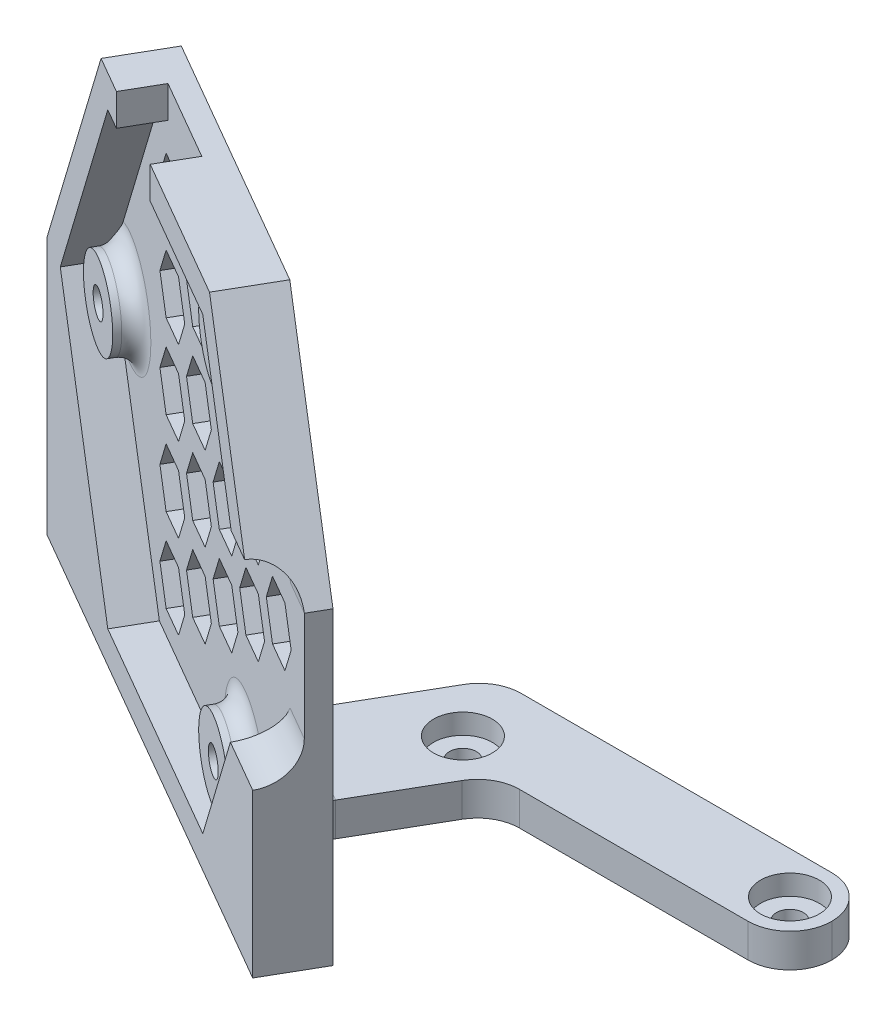
SolidWorks part; units mm, degrees
ref_plane "Plan de face" through (0, 0, 0) normal (0, 0, 1) x (1, 0, 0)
ref_plane "Plan de dessus" through (0, 0, 0) normal (0, 1, 0) x (1, 0, 0)
ref_plane "Plan de droite" through (0, 0, 0) normal (1, 0, 0) x (0, 0, -1)
sketch "Esquisse1" plane through (0, 0, 0) normal (0, -1, 0) x (1, 0, 0)
  line L0 (-1.5106, -613.3585) -> (-0.6906, -614.7787) construction
  line L1 (-0.6906, -614.7787) -> (25.2902, -599.7787) construction
  line L2 (25.2902, -599.7787) -> (24.4702, -598.3585) construction
  line L3 (24.4702, -598.3585) -> (-1.5106, -613.3585) construction
  circle A0 centre (30.4658, -623.4307) radius 1.7
  circle A1 centre (66.5558, -626.3007) radius 1.7
  circle A3 centre (5.084, -609.1007) radius 5 construction
  dimension "D1" = 30
  dimension "D2" = 30
  dimension "D3" = 7.84
  dimension "D4" = 1.64
  dimension "D5" = 0.39
ref_plane "Plan1" through (266.0344, 0, -460.785) normal (-0.5, 0, 0.866) x (0.866, 0, 0.5)
ref_plane "Plan2" through (267.4294, 0, -463.2012) normal (-0.5, 0, 0.866) x (0.866, 0, 0.5)
sketch "Esquisse2" plane through (684.9869, 0, -222.1243) normal (0.5, 0, -0.866) x (-0.866, 0, -0.5)
  line L19 (775.1414, 56.5615) -> (775.1414, 4.6) construction
  line L20 (776.8014, 58.1615) -> (776.8014, 56.5615) construction
  line L21 (787.8014, 56.5615) -> (776.8014, 56.5615) construction
  line L22 (787.8014, 58.1615) -> (787.8014, 56.5615) construction
  line L23 (787.8014, 58.1615) -> (776.8014, 58.1615) construction
  line L24 (748.0281, 35.5808) -> (760.1414, 56.5615) construction
  line L25 (760.1414, 4.6) -> (748.0281, 25.5808) construction
  line L26 (790.1414, 4.6) -> (760.1414, 4.6) construction
  line L27 (805.1414, 30.5808) -> (790.1414, 4.6) construction
  line L28 (790.1414, 56.5615) -> (805.1414, 30.5808) construction
  line L29 (760.1414, 56.5615) -> (790.1414, 56.5615) construction
  line L30 (748.0281, 35.5808) -> (748.0281, 25.5808) construction
  line L31 (790.1414, 0) -> (760.1414, 0) construction
  point P1 (787.8014, 57.3615)
  dimension "D1" = 30
  dimension "D2" = 20.9808
  dimension "D3" = 10
  dimension "D4" = 20.9808
  dimension "D5" = 30
  dimension "D6" = 30
  dimension "D7" = 30
  dimension "D8" = 51.9615
  dimension "D9" = 120
  dimension "D10" = 120
  dimension "D11" = 120
  dimension "D12" = 120
  dimension "D13" = 120
  dimension "D14" = 150
  dimension "D15" = 150
  dimension "D16" = 15
  dimension "D17" = 2.34
  dimension "D18" = 11
  dimension "D19" = 1.6
  dimension "D20" = 11
  dimension "D21" = 1.6
  dimension "D22" = 90
  dimension "D23" = 90
  dimension "D24" = 0
  dimension "D25" = 4.6
  dimension "D26" = 0
  dimension "D27" = 0
sketch "Esquisse3" plane through (267.4294, 0, -463.2012) normal (-0.5, 0, 0.866) x (0.866, 0, 0.5)
  line L7 (-275.3316, 61.1615) -> (-310.6433, 61.1615)
  line L8 (-310.6433, 61.1615) -> (-328.2991, 30.5808)
  line L9 (-328.2991, 30.5808) -> (-310.6433, 0)
  line L10 (-310.6433, 0) -> (-275.3316, 0)
  line L11 (-275.3316, 0) -> (-261.2742, 24.3482)
  line L12 (-261.2742, 24.3482) -> (-261.2742, 36.8133)
  line L13 (-261.2742, 36.8133) -> (-275.3316, 61.1615)
  line L14 (-277.5256, 57.3615) -> (-308.4493, 57.3615)
  line L15 (-265.0742, 35.7951) -> (-277.5256, 57.3615)
  line L16 (-265.0742, 25.3664) -> (-265.0742, 35.7951)
  line L17 (-277.5256, 3.8) -> (-265.0742, 25.3664)
  line L18 (-308.4493, 3.8) -> (-277.5256, 3.8)
  line L19 (-323.9112, 30.5808) -> (-308.4493, 3.8)
  line L20 (-308.4493, 57.3615) -> (-323.9112, 30.5808)
  line L21 (-277.5256, 57.3615) -> (-308.4493, 57.3615)
  line L22 (-265.0742, 35.7951) -> (-277.5256, 57.3615)
  line L23 (-265.0742, 25.3664) -> (-265.0742, 35.7951)
  line L24 (-277.5256, 3.8) -> (-265.0742, 25.3664)
  line L25 (-308.4493, 3.8) -> (-277.5256, 3.8)
  line L26 (-323.9112, 30.5808) -> (-308.4493, 3.8)
  line L27 (-308.4493, 57.3615) -> (-323.9112, 30.5808)
  line L28 (28.092, 0) -> (-28.092, 0) construction
  dimension "D2" = 0
  dimension "D1" = 0.8
extrude "Boss.-Extru.1" add sketch "Esquisse3" along normal blind 4.5
sketch "Esquisse4" plane through (267.4294, 0, -463.2012) normal (-0.5, 0, 0.866) x (0.866, 0, 0.5)
  line L0 (-310.6433, 61.1615) -> (-275.3316, 61.1615)
  line L1 (-275.3316, 61.1615) -> (-261.2742, 36.8133)
  line L2 (-261.2742, 36.8133) -> (-261.2742, 24.3482)
  line L3 (-261.2742, 24.3482) -> (-275.3316, 0)
  line L4 (-275.3316, 0) -> (-310.6433, 0)
  line L5 (-310.6433, 0) -> (-328.2991, 30.5808)
  line L6 (-328.2991, 30.5808) -> (-310.6433, 61.1615)
extrude "Boss.-Extru.2" add sketch "Esquisse4" against normal blind 2.5
sketch "Esquisse5" plane through (267.4294, 0, -463.2012) normal (-0.5, 0, 0.866) x (0.866, 0, 0.5)
  line L0 (-305.6475, 57.3615) -> (-305.6475, 61.1615)
  line L1 (-305.6475, 58.1615) -> (-305.6475, 56.5615) construction
  line L2 (-275.3316, 61.1615) -> (-310.6433, 61.1615) construction
  line L3 (-305.6475, 61.1615) -> (-294.6475, 61.1615)
  line L4 (-294.6475, 61.1615) -> (-294.6475, 57.3615)
  line L5 (-294.6475, 58.1615) -> (-294.6475, 56.5615) construction
  line L6 (-294.6475, 57.3615) -> (-305.6475, 57.3615)
extrude "Enlèv. mat.-Extru.1" cut sketch "Esquisse5" along normal up to next
sketch "Esquisse6" plane through (267.4294, 0, -463.2012) normal (-0.5, 0, 0.866) x (0.866, 0, 0.5)
  line L0 (-292.9875, 30.5808) -> (-280.4875, 52.2314) construction
  line L1 (-292.9875, 56.5615) -> (-292.9875, 4.6) construction
  line L2 (-292.9875, 30.5808) -> (-280.4875, 8.9301) construction
  line L3 (-292.9875, 30.5808) -> (-317.9875, 30.5808) construction
  circle A0 centre (-280.4875, 52.2314) radius 4.75
  circle A1 centre (-280.4875, 8.9301) radius 4.75
  circle A2 centre (-317.9875, 30.5808) radius 4.75
  dimension "D6" = 9.5
  dimension "D7" = 9.5
  dimension "D8" = 9.5
  dimension "D1" = 25
  dimension "D2" = 25
  dimension "D3" = 25
  dimension "D4" = 120
  dimension "D5" = 120
extrude "Boss.-Extru.3" add sketch "Esquisse6" along normal up to surface (2.79 mm away) up to plane "Plan1"
sketch "Esquisse7" plane through (267.4294, 0, -463.2012) normal (-0.5, 0, 0.866) x (0.866, 0, 0.5)
  line L0 (-328.2991, 30.5808) -> (-328.2991, 0)
  line L1 (-328.2991, 0) -> (-310.6433, 0)
  line L2 (-310.6433, 0) -> (-328.2991, 30.5808)
  line L3 (-275.3316, 0) -> (-261.2742, 24.3482)
  line L4 (-261.2742, 24.3482) -> (-261.2742, 0)
  line L5 (-261.2742, 0) -> (-275.3316, 0)
  dimension "D2" = 14.0574
extrude "Boss.-Extru.4" add sketch "Esquisse7" along normal up to surface (4.5 mm away) and the other way up to surface (2.5 mm away) up to face at (12.6176, 36.9543, -605.1207) other way up to face at (18.4231, 30.5808, -609.8518)
hole_wizard "Dégagement M31" positions "Esquisse9" profile "Esquisse10" hole size "M3" standard "Ansi Metric"
sketch "Esquisse9" plane through (266.0344, 0, -460.785) normal (-0.5, 0, 0.866) x (0.866, 0, 0.5)
  point P0 (-317.9875, 30.5808)
  point P3 (-280.4875, 52.2314)
  point P6 (-280.4875, 8.9301)
sketch "Esquisse10" plane through (-9.3509, 30.5808, -619.7787) normal (0, 1, 0) x (0.866, 0, 0.5)
  line L0 (0, 0) -> (0, 3.9614)
  line L1 (0, 3.9614) -> (1.6, 3)
  line L2 (1.6, 3) -> (1.6, 0)
  line L5 (1.6, 0) -> (0, 0)
  line L10 (0, 3.9614) -> (-1.6, 3) construction
  line L11 (0, -6.35) -> (0, 107.95) construction
  dimension "Diamètre du perçage" = 3.2
  dimension "Profondeur du perçage" = 3
  dimension "Angle de pointe" = 118
sketch "Esquisse11" plane through (143.5957, 0, -534.6966) normal (-0.5, 0, 0.866) x (0.866, 0, 0.5)
  line L0 (-162.6567, 56.5615) -> (-151.6567, 56.5615) construction
  line L1 (-159.2247, 53.5615) -> (-163.2647, 53.5615)
  line L2 (-163.2647, 53.5615) -> (-165.2847, 50.0628)
  line L3 (-165.2847, 50.0628) -> (-163.2647, 46.564)
  line L4 (-163.2647, 46.564) -> (-159.2247, 46.564)
  line L5 (-159.2247, 46.564) -> (-157.2047, 50.0628)
  line L6 (-157.2047, 50.0628) -> (-159.2247, 53.5615)
  line L7 (-164.9967, 56.5615) -> (-179.9967, 30.5808) construction
  line L8 (-150.5666, 41.5653) -> (-148.5466, 45.064)
  line L9 (-148.5466, 45.064) -> (-150.5666, 48.5628)
  line L10 (-150.5666, 48.5628) -> (-154.6066, 48.5628)
  line L11 (-154.6066, 48.5628) -> (-156.6266, 45.064)
  line L12 (-156.6266, 45.064) -> (-154.6066, 41.5653)
  line L13 (-154.6066, 41.5653) -> (-150.5666, 41.5653)
  line L14 (-141.9085, 36.5666) -> (-139.8885, 40.0653)
  line L15 (-139.8885, 40.0653) -> (-141.9085, 43.564)
  line L16 (-141.9085, 43.564) -> (-145.9485, 43.564)
  line L17 (-145.9485, 43.564) -> (-147.9685, 40.0653)
  line L18 (-147.9685, 40.0653) -> (-145.9485, 36.5666)
  line L19 (-145.9485, 36.5666) -> (-141.9085, 36.5666)
  line L20 (-133.2504, 31.5678) -> (-131.2304, 35.0666)
  line L21 (-131.2304, 35.0666) -> (-133.2504, 38.5653)
  line L22 (-133.2504, 38.5653) -> (-137.2904, 38.5653)
  line L23 (-137.2904, 38.5653) -> (-139.3104, 35.0666)
  line L24 (-139.3104, 35.0666) -> (-137.2904, 31.5678)
  line L25 (-137.2904, 31.5678) -> (-133.2504, 31.5678)
  line L26 (-124.5924, 26.5691) -> (-122.5724, 30.0678)
  line L27 (-122.5724, 30.0678) -> (-124.5924, 33.5666)
  line L28 (-124.5924, 33.5666) -> (-128.6324, 33.5666)
  line L29 (-128.6324, 33.5666) -> (-130.6524, 30.0678)
  line L30 (-130.6524, 30.0678) -> (-128.6324, 26.5691)
  line L31 (-128.6324, 26.5691) -> (-124.5924, 26.5691)
  line L32 (-159.2247, 26.5691) -> (-157.2047, 30.0678)
  line L33 (-157.2047, 30.0678) -> (-159.2247, 33.5666)
  line L34 (-159.2247, 33.5666) -> (-163.2647, 33.5666)
  line L35 (-163.2647, 33.5666) -> (-165.2847, 30.0678)
  line L36 (-165.2847, 30.0678) -> (-163.2647, 26.5691)
  line L37 (-163.2647, 26.5691) -> (-159.2247, 26.5691)
  line L38 (-150.5666, 21.5703) -> (-148.5466, 25.0691)
  line L39 (-148.5466, 25.0691) -> (-150.5666, 28.5678)
  line L40 (-150.5666, 28.5678) -> (-154.6066, 28.5678)
  line L41 (-154.6066, 28.5678) -> (-156.6266, 25.0691)
  line L42 (-156.6266, 25.0691) -> (-154.6066, 21.5703)
  line L43 (-154.6066, 21.5703) -> (-150.5666, 21.5703)
  line L44 (-141.9085, 16.5716) -> (-139.8885, 20.0703)
  line L45 (-139.8885, 20.0703) -> (-141.9085, 23.5691)
  line L46 (-141.9085, 23.5691) -> (-145.9485, 23.5691)
  line L47 (-145.9485, 23.5691) -> (-147.9685, 20.0703)
  line L48 (-147.9685, 20.0703) -> (-145.9485, 16.5716)
  line L49 (-145.9485, 16.5716) -> (-141.9085, 16.5716)
  line L50 (-159.2247, 6.5741) -> (-157.2047, 10.0728)
  line L51 (-157.2047, 10.0728) -> (-159.2247, 13.5716)
  line L52 (-159.2247, 13.5716) -> (-163.2647, 13.5716)
  line L53 (-163.2647, 13.5716) -> (-165.2847, 10.0728)
  line L54 (-165.2847, 10.0728) -> (-163.2647, 6.5741)
  line L55 (-163.2647, 6.5741) -> (-159.2247, 6.5741)
  line L56 (-150.5666, 38.5653) -> (-154.6066, 38.5653)
  line L57 (-159.2247, 43.564) -> (-163.2647, 43.564)
  line L58 (-163.2647, 43.564) -> (-165.2847, 40.0653)
  line L59 (-165.2847, 40.0653) -> (-163.2647, 36.5666)
  line L60 (-163.2647, 36.5666) -> (-159.2247, 36.5666)
  line L61 (-159.2247, 36.5666) -> (-157.2047, 40.0653)
  line L62 (-157.2047, 40.0653) -> (-159.2247, 43.564)
  line L63 (-154.6066, 38.5653) -> (-156.6266, 35.0666)
  line L64 (-156.6266, 35.0666) -> (-154.6066, 31.5678)
  line L65 (-154.6066, 31.5678) -> (-150.5666, 31.5678)
  line L66 (-150.5666, 31.5678) -> (-148.5466, 35.0666)
  line L67 (-148.5466, 35.0666) -> (-150.5666, 38.5653)
  line L68 (-141.9085, 33.5666) -> (-145.9485, 33.5666)
  line L69 (-145.9485, 33.5666) -> (-147.9685, 30.0678)
  line L70 (-147.9685, 30.0678) -> (-145.9485, 26.5691)
  line L71 (-145.9485, 26.5691) -> (-141.9085, 26.5691)
  line L72 (-141.9085, 26.5691) -> (-139.8885, 30.0678)
  line L73 (-139.8885, 30.0678) -> (-141.9085, 33.5666)
  line L74 (-133.2504, 28.5678) -> (-137.2904, 28.5678)
  line L75 (-137.2904, 28.5678) -> (-139.3104, 25.0691)
  line L76 (-139.3104, 25.0691) -> (-137.2904, 21.5703)
  line L77 (-137.2904, 21.5703) -> (-133.2504, 21.5703)
  line L78 (-133.2504, 21.5703) -> (-131.2304, 25.0691)
  line L79 (-131.2304, 25.0691) -> (-133.2504, 28.5678)
  line L80 (-159.2247, 23.5691) -> (-163.2647, 23.5691)
  line L81 (-163.2647, 23.5691) -> (-165.2847, 20.0703)
  line L82 (-165.2847, 20.0703) -> (-163.2647, 16.5716)
  line L83 (-163.2647, 16.5716) -> (-159.2247, 16.5716)
  line L84 (-159.2247, 16.5716) -> (-157.2047, 20.0703)
  line L85 (-157.2047, 20.0703) -> (-159.2247, 23.5691)
  line L86 (-150.5666, 18.5703) -> (-154.6066, 18.5703)
  line L87 (-154.6066, 18.5703) -> (-156.6266, 15.0716)
  line L88 (-156.6266, 15.0716) -> (-154.6066, 11.5728)
  line L89 (-154.6066, 11.5728) -> (-150.5666, 11.5728)
  line L90 (-150.5666, 11.5728) -> (-148.5466, 15.0716)
  line L91 (-148.5466, 15.0716) -> (-150.5666, 18.5703)
  circle A0 centre (-161.2447, 50.0628) radius 3.4987 construction
  circle A1 centre (-161.2447, 40.0653) radius 3.4987 construction
  circle A2 centre (-152.5866, 35.0666) radius 3.4987 construction
  circle A3 centre (-143.9285, 30.0678) radius 3.4987 construction
  circle A4 centre (-135.2704, 25.0691) radius 3.4987 construction
  circle A5 centre (-161.2447, 20.0703) radius 3.4987 construction
  circle A6 centre (-152.5866, 15.0716) radius 3.4987 construction
  point P109 (-161.2447, 26.5691)
  dimension "D1" = 4.04
  dimension "D2" = 3
  dimension "D3" = 3
  dimension "D6" = 4.04
  dimension "D7" = 3
  dimension "D8" = 3
  dimension "D9" = 3
  dimension "D11" = 3
  dimension "D12" = 3
  dimension "D14" = 3
  dimension "D15" = 3
  dimension "D17" = 3
  dimension "D18" = 3
  dimension "D4" = 5
  dimension "D5" = 2
  dimension "D16" = 2
  dimension "D10" = 4
  dimension "D13" = 2
extrude "Enlèv. mat.-Extru.2" cut sketch "Esquisse11" against normal through all
ref_plane "USB-C" through (-229.561, 0, -132.5371) normal (-0.866, 0, -0.5) x (-0.5, 0, 0.866)
sketch "Esquisse12" plane through (-229.561, 0, -132.5371) normal (-0.866, 0, -0.5) x (-0.5, 0, 0.866)
  line L0 (-530.3587, 36.8664) -> (-530.3587, 23.8664) construction
  line L1 (-525.8587, 36.8664) -> (-525.8587, 23.8664)
  line L2 (-534.8587, 36.8664) -> (-534.8587, 23.8664)
  line L3 (-534.8587, 56.5615) -> (-534.8587, 30.5808) construction
  line L4 (-534.8587, 30.5808) -> (-534.8587, 4.6) construction
  line L5 (-534.8587, 25.3664) -> (-534.8587, 35.7951) construction
  arc A0 (-525.8587, 36.8664) -> (-534.8587, 36.8664) centre (-530.3587, 36.8664) ccw
  arc A1 (-534.8587, 23.8664) -> (-525.8587, 23.8664) centre (-530.3587, 23.8664) ccw
  point P2 (-530.3587, 30.3664)
  dimension "D6" = 1.5
  dimension "D1" = 13
  dimension "D2" = 9
  dimension "D3" = 0
  dimension "D4" = 9
  dimension "D5" = 4.5
extrude "Enlèv. mat.-Extru.3" cut sketch "Esquisse12" against normal blind 4 and the other way blind 4
sketch "Esquisse15" plane through (0, 0, 0) normal (0, 1, 0) x (1, 0, 0)
  line L0 (26.9879, 604.9069) -> (36.4529, 621.3007)
  line L1 (36.4529, 621.3007) -> (71.5558, 621.3007)
  line L2 (71.5558, 621.3007) -> (71.5558, 631.3007)
  line L3 (71.5558, 631.3007) -> (26.638, 631.3007)
  line L4 (26.638, 631.3007) -> (15.2966, 611.6569)
  line L5 (30.2352, 603.0321) -> (-0.3456, 620.6879) construction
  line L6 (15.2966, 611.6569) -> (26.9879, 604.9069)
  dimension "D1" = 5
  dimension "D2" = 90
  dimension "D3" = 90
  dimension "D4" = 120
  dimension "D5" = 120
  dimension "D6" = 90
  dimension "D7" = 90
  dimension "D8" = 5
  dimension "D9" = 5
  dimension "D10" = 13.5
  dimension "D11" = 6.25
  dimension "D12" = 7.25
extrude "Boss.-Extru.6" add sketch "Esquisse15" along normal blind 4
hole_wizard "Chambrage pour vis à tête ronde bombée M32" positions "Esquisse16" profile "Esquisse17" counterbore size "M3" standard "Ansi Metric" end condition through all
sketch "Esquisse16" plane through (0, 4, 0) normal (0, 1, 0) x (1, 0, 0)
  point P0 (30.4658, 623.4307)
  point P3 (66.5558, 626.3007)
sketch "Esquisse17" plane through (30.4658, 4, -623.4307) normal (1, 0, 0) x (0, 0, 1)
  line L0 (0, 0) -> (0, 4)
  line L1 (0, 4) -> (1.6, 4)
  line L3 (1.6, 4) -> (1.6, 2.4)
  line L4 (1.6, 2.4) -> (3.5, 2.4)
  line L5 (3.5, 2.4) -> (3.5, 0)
  line L7 (3.5, 0) -> (0, 0)
  line L11 (0, -6.35) -> (0, 107.95) construction
  dimension "Diamètre du perçage jusqu'au prochain" = 3.2
  dimension "Profondeur du perçage jusqu'au prochain" = 4
  dimension "Diamètre du chambrage" = 7
  dimension "Profondeur du chambrage" = 2.4
fillet "Congé2" radius 5 7 edges at (26.9879, 2, -604.9069) (21.1423, 4, -608.2819) (15.2966, 2, -611.6569) (26.638, 2, -631.3007) (71.5558, 2, -631.3007) (71.5558, 2, -621.3007) (36.4529, 2, -621.3007)
fillet "Congé3" radius 2 3 edges at (28.6337, 8.9301, -601.07) (28.6337, 52.2314, -601.07) (-3.8422, 30.5808, -619.82)
